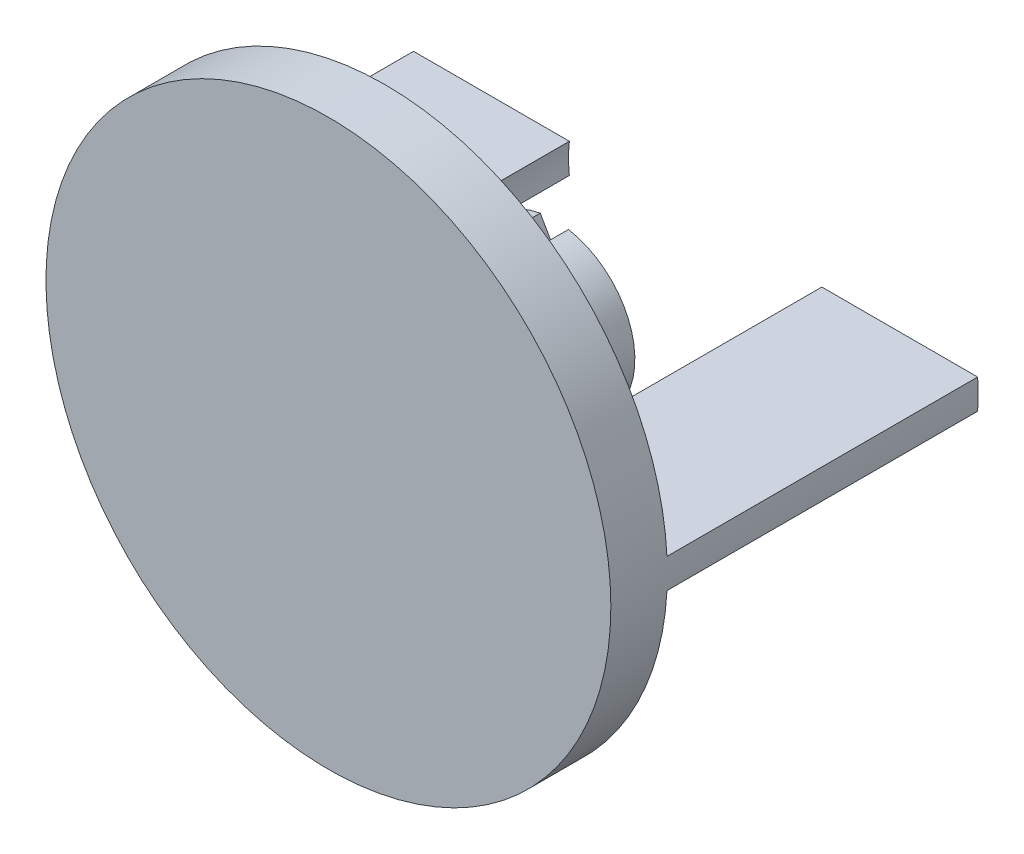
SolidWorks part; units mm, degrees
ref_plane "Front Plane" through (0, 0, 0) normal (0, 0, 1) x (1, 0, 0)
ref_plane "Top Plane" through (0, 0, 0) normal (0, 1, 0) x (1, 0, 0)
ref_plane "Right Plane" through (0, 0, 0) normal (1, 0, 0) x (0, 0, -1)
sketch "Sketch1" plane through (0, 0, 0) normal (0, 0, 1) x (1, 0, 0)
  circle A0 centre (0, 0) radius 2.85
  dimension "D1" = 5.7
extrude "Boss-Extrude1" add sketch "Sketch1" along normal blind 1 contours A0
sketch "Sketch2" plane through (0, 0, 1) normal (0, 0, 1) x (1, 0, 0)
  circle A0 centre (0, 0) radius 10
  dimension "D1" = 20
extrude "Boss-Extrude2" add sketch "Sketch2" along normal blind 2
sketch "Sketch3" plane through (0, 0, 1) normal (0, 0, -1) x (-1, 0, 0)
  line L0 (-10, 0.525) -> (-9.9862, 0.525) construction
  line L4 (-9.9862, 0.525) -> (9.9862, 0.525)
  line L5 (-10, 0.525) -> (-10, -0.525) construction
  line L6 (-9.9862, -0.525) -> (9.9862, -0.525)
  line L7 (10, 0.525) -> (10, -0.525) construction
  line L8 (-9.9862, 0.5243) -> (9.9862, -0.5243) construction
  line L9 (-9.9862, -0.5243) -> (9.9862, 0.5243) construction
  line L10 (-10, 0.525) -> (-9.9862, 0.5243) construction
  line L11 (-10, -0.525) -> (-9.9862, -0.5243) construction
  line L12 (-10, -0.525) -> (-9.9862, -0.525) construction
  line L13 (9.9862, 0.525) -> (10, 0.525) construction
  line L14 (9.9862, 0.5243) -> (10, 0.525) construction
  line L15 (9.9862, -0.5243) -> (10, -0.525) construction
  line L16 (9.9862, -0.525) -> (10, -0.525) construction
  arc A0 (9.9862, 0.525) -> (-9.9862, 0.525) centre (0, 0) ccw construction
  arc A3 (-9.9862, -0.525) -> (9.9862, -0.525) centre (0, 0) ccw construction
  circle A4 centre (0, 0) radius 10
  arc A5 (-9.9862, 0.525) -> (-9.9862, -0.525) centre (0, 0) ccw
  arc A6 (9.9862, -0.525) -> (9.9862, 0.525) centre (0, 0) ccw
  point P0 (0, 0)
  dimension "D2" = 1.05
  dimension "D1" = 0
  dimension "D3" = 20
extrude "Boss-Extrude3" add sketch "Sketch3" along normal blind 1
sketch "Sketch4" plane through (0, 0, 0) normal (0, 0, -1) x (-1, 0, 0)
  line L2 (-0.5, 2.8058) -> (0, 1.9398)
  line L3 (0, 1.9398) -> (0.5, 2.8058)
  line L6 (-2.8012, 0.525) -> (-9.9862, 0.525)
  line L7 (-9.9862, -0.525) -> (-2.8012, -0.525)
  line L8 (2.8012, -0.525) -> (9.9862, -0.525)
  line L9 (9.9862, 0.525) -> (2.8012, 0.525)
  line L10 (-2.8012, 0.525) -> (-9.9862, 0.525) construction
  line L11 (-9.9862, -0.525) -> (-2.8012, -0.525) construction
  line L12 (2.8012, -0.525) -> (9.9862, -0.525) construction
  line L13 (9.9862, 0.525) -> (2.8012, 0.525) construction
  arc A0 (2.8012, 0.525) -> (-2.8012, 0.525) centre (0, 0) ccw construction
  arc A2 (2.8012, 0.525) -> (0.5, 2.8058) centre (0, 0) ccw construction
  arc A3 (-0.5, 2.8058) -> (-2.8012, 0.525) centre (0, 0) ccw construction
  arc A5 (2.8012, 0.525) -> (-2.8012, 0.525) centre (0, 0) ccw
  arc A6 (-9.9862, 0.525) -> (-9.9862, -0.525) centre (0, 0) ccw
  arc A7 (-2.8012, -0.525) -> (2.8012, -0.525) centre (0, 0) ccw
  arc A8 (9.9862, -0.525) -> (9.9862, 0.525) centre (0, 0) ccw
  arc A9 (0.5, 2.8058) -> (-0.5, 2.8058) centre (0, 0) ccw
  arc A10 (-9.9862, 0.525) -> (-9.9862, -0.525) centre (0, 0) ccw
  arc A11 (-2.8012, -0.525) -> (2.8012, -0.525) centre (0, 0) ccw construction
  arc A12 (9.9862, -0.525) -> (9.9862, 0.525) centre (0, 0) ccw
  point P3 (0, 0)
  point P12 (0, 2.85)
  point P15 (0.5853, 2.7573)
  point P17 (-0.3587, 2.8273)
  arc M12 (2.8012, 0.525) -> (-2.8012, 0.525) centre (0, 0) ccw
  dimension "D1" = 0
  dimension "D2" = 1
  dimension "D3" = 60
extrude "Cut-Extrude1" cut sketch "Sketch4" against normal up to surface (1 mm away) contours L2 L3 M12 region at (0, 2.5367, 0) up to face at (0, -3.475, 1)
sketch "Sketch5" plane through (0, 0, 0) normal (0, 0, -1) x (-1, 0, 0)
  line L6 (0.5, 2.8058) -> (0, 1.9398)
  line L7 (0.5, 2.8058) -> (0, 1.9398)
  line L8 (-2.8012, 0.525) -> (-9.9862, 0.525)
  line L10 (-9.9862, -0.525) -> (-2.8012, -0.525)
  line L18 (2.8012, -0.525) -> (9.9862, -0.525)
  line L20 (9.9862, 0.525) -> (2.8012, 0.525)
  line L22 (0, 1.9398) -> (-0.5, 2.8058)
  line L23 (0, 1.9398) -> (-0.5, 2.8058)
  arc A6 (-9.9862, 0.525) -> (-9.9862, -0.525) centre (0, 0) ccw
  arc A16 (-2.8012, -0.525) -> (2.8012, -0.525) centre (0, 0) ccw
  arc A17 (-2.8012, -0.525) -> (2.8012, -0.525) centre (0, 0) ccw
  arc A18 (9.9862, -0.525) -> (9.9862, 0.525) centre (0, 0) ccw
  arc A19 (9.9862, -0.525) -> (9.9862, 0.525) centre (0, 0) ccw construction
  arc A20 (2.8012, 0.525) -> (0.5, 2.8058) centre (0, 0) ccw
  arc A21 (2.8012, -0.525) -> (0.5, 2.8058) centre (0, 0) ccw
  arc A22 (-0.5, 2.8058) -> (-2.8012, 0.525) centre (0, 0) ccw
  arc A23 (-0.5, 2.8058) -> (-2.8012, -0.525) centre (0, 0) ccw
  point P2 (-2.5954, -0.154)
  point P3 (2.8012, 0.525)
  point P4 (2.5954, -0.1553)
  point P9 (-2.8012, -0.3706)
  point P11 (2.8012, -0.3781)
  point P20 (0, 0)
  dimension "D1" = 0
extrude "Boss-Extrude4" add sketch "Sketch5" along normal blind 5 contours A17 A21 L7 L23 A23
sketch "Sketch6" plane through (0, 0, 0) normal (0, 0, -1) x (-1, 0, 0)
  line L0 (-2.8012, 0.525) -> (-4.4693, 0.525) construction
  line L1 (-4.4693, -0.525) -> (-2.8012, -0.525) construction
  line L2 (-2.8012, 0.525) -> (-9.9862, 0.525)
  line L3 (-9.9862, -0.525) -> (-2.8012, -0.525)
  line L4 (-4.4693, 0.525) -> (-9.9862, 0.525)
  line L5 (-9.9862, -0.525) -> (-4.4693, -0.525)
  line L6 (2.8012, -0.525) -> (9.9862, -0.525)
  line L7 (9.9862, 0.525) -> (2.8012, 0.525)
  line L8 (4.4693, -0.525) -> (9.9862, -0.525)
  line L9 (9.9862, 0.525) -> (4.4693, 0.525)
  line L10 (2.8012, -0.525) -> (4.4693, -0.525) construction
  line L11 (4.4693, 0.525) -> (2.8012, 0.525) construction
  arc A0 (-4.4693, 0.525) -> (-4.4693, -0.525) centre (0, 0) ccw
  arc A1 (4.4693, 0.525) -> (-4.4693, 0.525) centre (0, 0) ccw construction
  arc A2 (-2.8012, 0.525) -> (-2.8012, -0.525) centre (0, 0) ccw
  arc A3 (-9.9862, 0.525) -> (-9.9862, -0.525) centre (0, 0) ccw
  arc A4 (-2.8012, 0.525) -> (-2.8012, -0.525) centre (0, 0) ccw
  arc A5 (-9.9862, 0.525) -> (-9.9862, -0.525) centre (0, 0) ccw
  arc A6 (2.8012, -0.525) -> (2.8012, 0.525) centre (0, 0) ccw
  arc A7 (9.9862, -0.525) -> (9.9862, 0.525) centre (0, 0) ccw
  arc A8 (2.8012, -0.525) -> (2.8012, 0.525) centre (0, 0) ccw
  arc A9 (9.9862, -0.525) -> (9.9862, 0.525) centre (0, 0) ccw
  arc A10 (-4.4693, -0.525) -> (4.4693, -0.525) centre (0, 0) ccw construction
  arc A11 (4.4693, -0.525) -> (4.4693, 0.525) centre (0, 0) ccw
  line M11 (-2.8012, 0.525) -> (-9.9862, 0.525)
  arc M12 (-9.9862, 0.525) -> (-9.9862, -0.525) centre (0, 0) ccw
  line M13 (-9.9862, -0.525) -> (-2.8012, -0.525)
  dimension "D3" = 9
  dimension "D1" = 0
  dimension "D2" = 0
extrude "Boss-Extrude5" add sketch "Sketch6" along normal blind 10 contours A0 M11 M12 M13 | A11 L8 A9 L9 region at (7.2426, 0, 0) region at (-7.2426, 0, 0)
